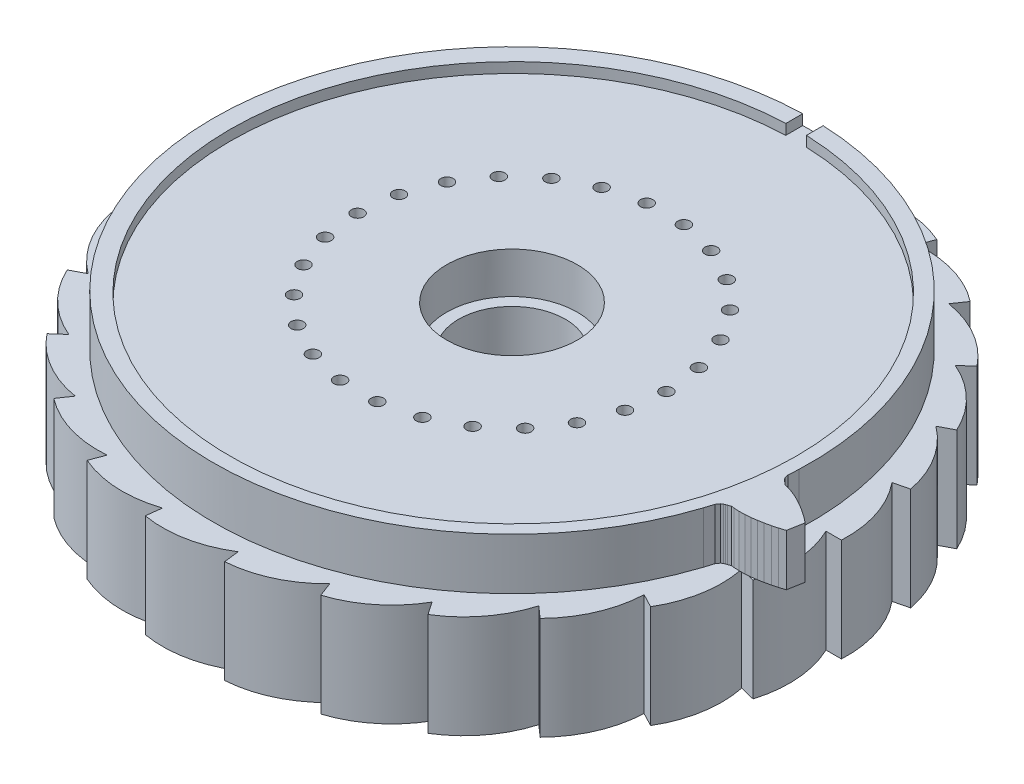
SolidWorks part; units mm, degrees
material "1060 Alloy"
ref_plane "Front Plane" through (0, 0, 0) normal (0, 0, 1) x (1, 0, 0)
ref_plane "Top Plane" through (0, 0, 0) normal (0, 1, 0) x (1, 0, 0)
ref_plane "Right Plane" through (0, 0, 0) normal (1, 0, 0) x (0, 0, -1)
sketch "Sketch1" plane through (0, 0, 0) normal (0, 1, 0) x (1, 0, 0)
  line L0 (0, 0) -> (54.8903, 0) construction
  line L1 (0, 0) -> (47.5263, 11.7142) construction
  line L2 (0, 0) -> (29.6137, 7.2991)
  line L3 (0, 0) -> (32, 0)
  circle A0 centre (0, 0) radius 32 construction
  circle A1 centre (0, 0) radius 30.5 construction
  arc A2 (29.6137, 7.2991) -> (32, 0) centre (21.3514, 0.5583) cw
  circle A3 centre (0, 0) radius 31.25 construction
  dimension "D1" = 62.5
  dimension "D2" = 1.5
  dimension "D4" = 0.75
  dimension "D3" = 13.846
extrude "Extrude ratchet edge" add sketch "Sketch1" along normal blind 10
pattern_circular "Pattern edge to form gear" count 26 over 360 about axis through (0, 10, 0) along (0, -1, 0) of "Extrude ratchet edge" reverse direction yes
sketch "Sketch12" plane through (0, 10, 0) normal (0, 1, 0) x (1, 0, 0)
  line L0 (28.9274, -2.1257) -> (29.0264, -2.5152)
  line L1 (29.0264, -2.5152) -> (29.1427, -2.6718)
  line L2 (29.1427, -2.6718) -> (29.2623, -2.7873)
  line L3 (29.2623, -2.7873) -> (29.3837, -2.8801)
  line L4 (29.3837, -2.8801) -> (29.6242, -3.0821)
  line L5 (29.6242, -3.0821) -> (29.8792, -3.1399)
  line L6 (29.8792, -3.1399) -> (30.3843, -3.2992)
  line L7 (30.3843, -3.2992) -> (30.8844, -3.4996)
  line L8 (30.8844, -3.4996) -> (31.3799, -3.7334)
  line L9 (31.3799, -3.7334) -> (31.8708, -3.9966)
  line L10 (31.8708, -3.9966) -> (32.3568, -4.2867)
  line L11 (32.3568, -4.2867) -> (32.8378, -4.602)
  line L12 (32.8378, -4.602) -> (33.3134, -4.9413)
  line L13 (33.3134, -4.9413) -> (33.7833, -5.3035)
  line L14 (33.7833, -5.3035) -> (33.502, -6.8593)
  line L15 (33.502, -6.8593) -> (32.9351, -7.0341)
  line L16 (32.9351, -7.0341) -> (32.3708, -7.1854)
  line L17 (32.3708, -7.1854) -> (31.8099, -7.3124)
  line L18 (31.8099, -7.3124) -> (31.253, -7.414)
  line L19 (31.253, -7.414) -> (30.7011, -7.4887)
  line L20 (30.7011, -7.4887) -> (30.1551, -7.5342)
  line L21 (30.1551, -7.5342) -> (29.6165, -7.5468)
  line L22 (29.6165, -7.5468) -> (29.0876, -7.5192)
  line L23 (29.0876, -7.5192) -> (28.8285, -7.4842)
  line L24 (28.8285, -7.4842) -> (28.5325, -7.5891)
  line L25 (28.5325, -7.5891) -> (28.3863, -7.6336)
  line L26 (28.3863, -7.6336) -> (28.2339, -7.6999)
  line L27 (28.2339, -7.6999) -> (28.07, -7.8059)
  line L28 (28.07, -7.8059) -> (27.841, -8.136)
  line L29 (27.841, -8.136) -> (27.578, -8.987)
  line L779 (28.9844, -1.1053) -> (28.9274, -2.1257)
  arc A0 (27.578, -8.987) -> (28.9844, -1.1053) centre (0, 0) cw
extrude "Gear face" add sketch "Sketch12" along normal blind 5
sketch "Sketch7" plane through (0, 15, 0) normal (0, 1, 0) x (1, 0, 0)
  circle A0 centre (0, 0) radius 6.35
  dimension "D1" = 12.7
sketch "Sketch10" plane through (0, 15, 0) normal (0, 1, 0) x (1, 0, 0)
  line L0 (-0.7538, 29.3517) -> (-0.7538, 27.3517)
  line L1 (1.2462, 27.3517) -> (1.2462, 29.3517)
  line L2 (1.2462, 29.3517) -> (-0.7538, 29.3517)
  line L3 (0.2462, -0.1301) -> (0.2462, 41.1735) construction
  line L4 (0.2462, -0.1301) -> (0.2462, 36.6199) construction
  arc A0 (-0.7538, 27.3517) -> (1.2462, 27.3517) centre (0.2462, -0.1301) ccw
  dimension "D1" = 2
extrude "PCB inset" cut sketch "Sketch10" against normal blind 1
extrude "Cut bearing hole" cut sketch "Sketch7" against normal up to surface (5 mm away) up to face at (32.4022, 10, 5.8482)
sketch "Sketch11" plane through (0, 0, 0) normal (0, -1, 0) x (1, 0, 0)
  line L0 (1, -29.4818) -> (1, -27.4818)
  line L1 (-1, -27.4818) -> (-1, -29.4818)
  line L2 (-1, -29.4818) -> (1, -29.4818)
  line L3 (0, 0) -> (0, -100.666) construction
  arc A0 (1, -27.4818) -> (-1, -27.4818) centre (0, 0) ccw
  point P0 (0, -29.4818)
  dimension "D2" = 2
  dimension "D3" = 27.5
  dimension "D1" = 2
  dimension "D4" = 2
extrude "PCB inset rear" cut sketch "Sketch11" against normal blind 1
sketch "pin holes" plane through (0, 14, 0) normal (0, 1, 0) x (1, 0, 0)
  circle A0 centre (15, 0) radius 0.6
  circle A1 centre (14.5641, -3.5897) radius 0.6
  circle A2 centre (13.2818, -6.9708) radius 0.6
  circle A3 centre (11.2277, -9.9468) radius 0.6
  circle A4 centre (8.521, -12.3448) radius 0.6
  circle A5 centre (5.3191, -14.0252) radius 0.6
  circle A6 centre (1.8081, -14.8906) radius 0.6
  circle A7 centre (-1.8081, -14.8906) radius 0.6
  circle A8 centre (-5.3191, -14.0252) radius 0.6
  circle A9 centre (-8.521, -12.3448) radius 0.6
  circle A10 centre (-11.2277, -9.9468) radius 0.6
  circle A11 centre (-13.2818, -6.9708) radius 0.6
  circle A12 centre (-14.5641, -3.5897) radius 0.6
  circle A13 centre (-15, 0) radius 0.6
  circle A14 centre (-14.5641, 3.5897) radius 0.6
  circle A15 centre (-13.2818, 6.9708) radius 0.6
  circle A16 centre (-11.2277, 9.9468) radius 0.6
  circle A17 centre (-8.521, 12.3448) radius 0.6
  circle A18 centre (-5.3191, 14.0252) radius 0.6
  circle A19 centre (-1.8081, 14.8906) radius 0.6
  circle A20 centre (1.8081, 14.8906) radius 0.6
  circle A21 centre (5.3191, 14.0252) radius 0.6
  circle A22 centre (8.521, 12.3448) radius 0.6
  circle A23 centre (11.2277, 9.9468) radius 0.6
  circle A24 centre (13.2818, 6.9708) radius 0.6
  circle A25 centre (14.5641, 3.5897) radius 0.6
  point P55 (0, 0)
  dimension "D1" = 1.2
  dimension "D2" = 15
  dimension "D3" = 26
extrude "Pin holes cut" cut sketch "pin holes" against normal through all
sketch "Sketch14" [suppressed] plane through (0, 14, 0) normal (0, 1, 0) x (1, 0, 0)
  line L0 (0, 0) -> (0, 34.7764) construction
  circle A0 centre (0, 25) radius 1.5875
  circle A1 centre (21.6506, -12.5) radius 1.5875
  circle A2 centre (-21.6506, -12.5) radius 1.5875
  point P11 (0, 0)
  dimension "D1" = 3.175
  dimension "D2" = 25
  dimension "D3" = 3
extrude "Cut-Extrude2" [suppressed] cut sketch "Sketch14" against normal through all
sketch "Sketch13" [suppressed] plane through (0, 10, 0) normal (0, 1, 0) x (1, 0, 0)
  circle A0 centre (0, 0) radius 52.9385
extrude "Cut in half for 3D print" [suppressed] cut sketch "Sketch13" along normal through all
sketch "Sketch15" plane through (0, 0, 0) normal (0, -1, 0) x (1, 0, 0)
  circle A0 centre (0, 0) radius 5.18
  dimension "D1" = 10.36
extrude "Cut-Extrude3" cut sketch "Sketch15" against normal through all
equation "\"Bearing size\"= 12.7mm"
equation "\"D1@Sketch7\" = \"Bearing size\""
equation "\"dedendum\"= 2mm"
equation "\"addendum\"= 2mm"
equation "\"D5@Iteration wheel\" = \"addendum\""
equation "\"base diameter\"=58"
equation "\"alpha\"= sqr ( ( \"base diameter\" + \"dedendum\" ) ^ 2 - \"base diameter\" ^ 2 ) / \"base diameter\" * 180 / PI - \"phi\""
equation "\"phi\"= 20"
